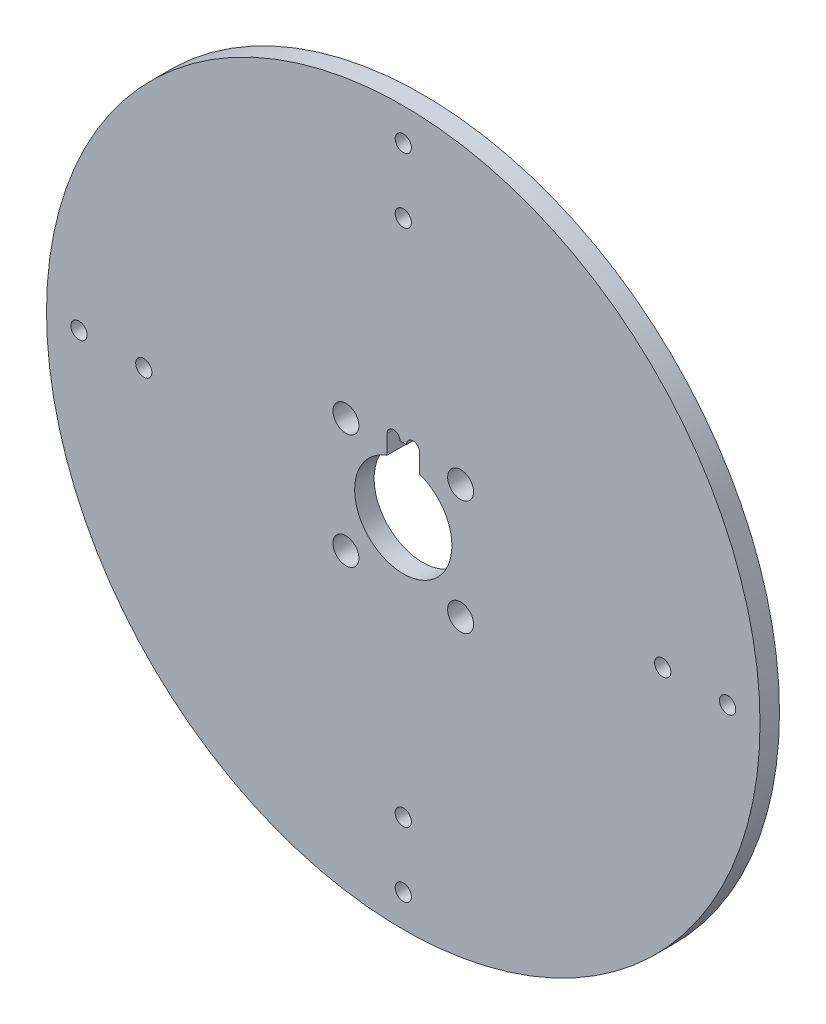
SolidWorks part; units mm, degrees
note: The reader was unsure of these and kept them because the rebuilt part matched: shared geometry of "ｽｹｯﾁ1<4>".
material "3.1325 (EN-AW 2017A)"
ref_plane "正面" through (0, 0, 0) normal (0, 0, 1) x (1, 0, 0)
ref_plane "平面" through (0, 0, 0) normal (0, 1, 0) x (1, 0, 0)
ref_plane "右側面" through (0, 0, 0) normal (1, 0, 0) x (0, 0, -1)
sketch "ｽｹｯﾁ1" plane through (0, 0, 0) normal (0, 0, 1) x (1, 0, 0)
  line L0 (0, 0) -> (0, 55) construction
  line L1 (-2.5, 7.0711) -> (-2.5, 10)
  line L2 (-0.5, 10) -> (0.5, 10)
  line L3 (2.5, 10) -> (2.5, 7.0711)
  line L4 (0, 0) -> (8.8388, 8.8388) construction
  line L5 (-2.5, 5) -> (2.5, 5) construction
  line L6 (-2.5, 5) -> (-2.5, 10) construction
  line L7 (-2.5, 10) -> (2.5, 10) construction
  line L8 (2.5, 5) -> (2.5, 10) construction
  circle A0 centre (0, 0) radius 55
  arc A1 (-2.5, 7.0711) -> (2.5, 7.0711) centre (0, 0) ccw
  arc A2 (0.5, 10) -> (2.5, 10) centre (1.5, 10) cw
  arc A3 (-2.5, 10) -> (-0.5, 10) centre (-1.5, 10) cw
  circle A4 centre (0, 0) radius 12.5 construction
  point P3 (8.8388, 8.8388)
  point P17 (0, 10)
  point P18 (0, 20.5)
  point P19 (0, 40)
  point P20 (0, 50)
  point P22 (0, 10)
  point P24 (8.8388, -8.8388)
  point P25 (20.5, 0)
  point P26 (40, 0)
  point P27 (50, 0)
  point P28 (-8.8388, -8.8388)
  point P29 (0, -20.5)
  point P30 (0, -40)
  point P31 (0, -50)
  point P32 (-8.8388, 8.8388)
  point P33 (-20.5, 0)
  point P34 (-40, 0)
  point P35 (-50, 0)
  point P36 (0, 0)
  dimension "D1" = 110
  dimension "D2" = 15
  dimension "D3" = 2
  dimension "D6" = 25
  dimension "D4" = 2.5
  dimension "D5" = 5
  dimension "D7" = 45
  dimension "D9" = 20.5
  dimension "D10" = 40
  dimension "D11" = 50
  dimension "D8" = 4
extrude "ﾎﾞｽ - 押し出し1" add sketch "ｽｹｯﾁ1" along normal mid plane 3 contours A0
extrude "ｶｯﾄ - 押し出し7" cut sketch "ｽｹｯﾁ1<4>" against normal through all both and the other way through all contours A3 L1 A1 L3 A2 L2
sketch "ｽｹｯﾁ1<4>" plane through (0, 0, 0) normal (0, 0, 1) x (1, 0, 0) same geometry as "ｽｹｯﾁ1"
hole_wizard "M4 すきま穴1" [suppressed] positions "3Dｽｹｯﾁ5" profile "ｽｹｯﾁ3" hole size "M4" standard "JIS"
sketch3d "3Dｽｹｯﾁ5"
  point P0 (-8.8388, 8.8388, 1.5)
  point P2 (8.8388, 8.8388, 1.5)
  point P4 (8.8388, -8.8388, 1.5)
  point P6 (-8.8388, -8.8388, 1.5)
sketch "ｽｹｯﾁ3" plane through (-8.8388, 8.8388, 1.5) normal (1, 0, 0) x (0, -1, 0)
  line L0 (0, 0) -> (0, 3)
  line L1 (0, 3) -> (2.15, 3)
  line L2 (2.15, 3) -> (2.15, 0)
  line L5 (2.15, 0) -> (0, 0)
  line L11 (0, -6.35) -> (0, 107.95) construction
  dimension "通し穴の直径" = 4.3
  dimension "通し穴の深さ" = 3
hole_wizard "M5 丸皿ねじ用皿穴1" [suppressed] positions "3Dｽｹｯﾁ7" profile "ｽｹｯﾁ4" countersink size "M5" standard "JIS"
sketch3d "3Dｽｹｯﾁ7"
  point P0 (0, 0, 1.5)
sketch "ｽｹｯﾁ4" plane through (0, 0, 1.5) normal (1, 0, 0) x (0, -1, 0)
  line L0 (0, 0) -> (0, 3)
  line L1 (0, 3) -> (2.65, 3)
  line L2 (2.65, 3) -> (2.65, 2.55)
  line L3 (2.65, 2.55) -> (5.2, 0)
  line L5 (5.2, 0) -> (0, 0)
  line L6 (-2.65, 2.55) -> (-5.2, 0) construction
  line L11 (0, -6.35) -> (0, 107.95) construction
  dimension "通し穴の直径" = 5.3
  dimension "通し穴の深さ" = 3
  dimension "表面の皿穴の直径" = 10.4
  dimension "表面の皿穴の角度" = 90
hole_wizard "M3x0.5 ねじ穴1" positions "3Dｽｹｯﾁ4" profile "ｽｹｯﾁ2" tap size "M3x0.5" standard "JIS" end condition through all
sketch3d "3Dｽｹｯﾁ4"
  point P0 (0, 50, 1.5)
  point P2 (0, 40, 1.5)
  point P4 (-50, 0, 1.5)
  point P6 (-40, 0, 1.5)
  point P8 (0, -50, 1.5)
  point P10 (0, -40, 1.5)
  point P12 (50, 0, 1.5)
  point P14 (40, 0, 1.5)
sketch "ｽｹｯﾁ2" plane through (0, 50, 1.5) normal (1, 0, 0) x (0, -1, 0)
  line L0 (0, 0) -> (0, 3)
  line L1 (0, 3) -> (1.25, 3)
  line L2 (1.25, 3) -> (1.25, 0)
  line L5 (1.25, 0) -> (0, 0)
  line L11 (0, -6.35) -> (0, 107.95) construction
  dimension "ねじ山の主要直径" = 2.5
  dimension "次ｻｰﾌｪｽまでのねじ下穴ﾄﾞﾘﾙの深さ" = 3
hole_wizard "Ø4.0mm ﾀﾞｳｴﾙ穴1" positions "ｽｹｯﾁ6" profile "ｽｹｯﾁ5" hole size "Ø4.0" standard "JIS"
sketch "ｽｹｯﾁ6" plane through (0, 0, 1.5) normal (0, 0, 1) x (1, 0, 0)
  point P0 (-8.8388, -8.8388)
  point P2 (-8.8388, 8.8388)
  point P4 (8.8388, 8.8388)
  point P6 (8.8388, -8.8388)
sketch "ｽｹｯﾁ5" plane through (-8.8388, -8.8388, 1.5) normal (1, 0, 0) x (0, -1, 0)
  line L0 (0, 0) -> (0, 6.2017)
  line L1 (0, 6.2017) -> (2, 5)
  line L2 (2, 5) -> (2, 0)
  line L5 (2, 0) -> (0, 0)
  line L10 (0, 6.2017) -> (-2, 5) construction
  line L11 (0, -6.35) -> (0, 107.95) construction
  dimension "穴の直径" = 4
  dimension "穴の深さ" = 5
  dimension "ﾄﾞﾘﾙ角度" = 118
equation "\"ミル径\"= 1"
equation "\"コーナR面取り小\"= 2"
equation "\"コーナR面取り大\"= 5"
